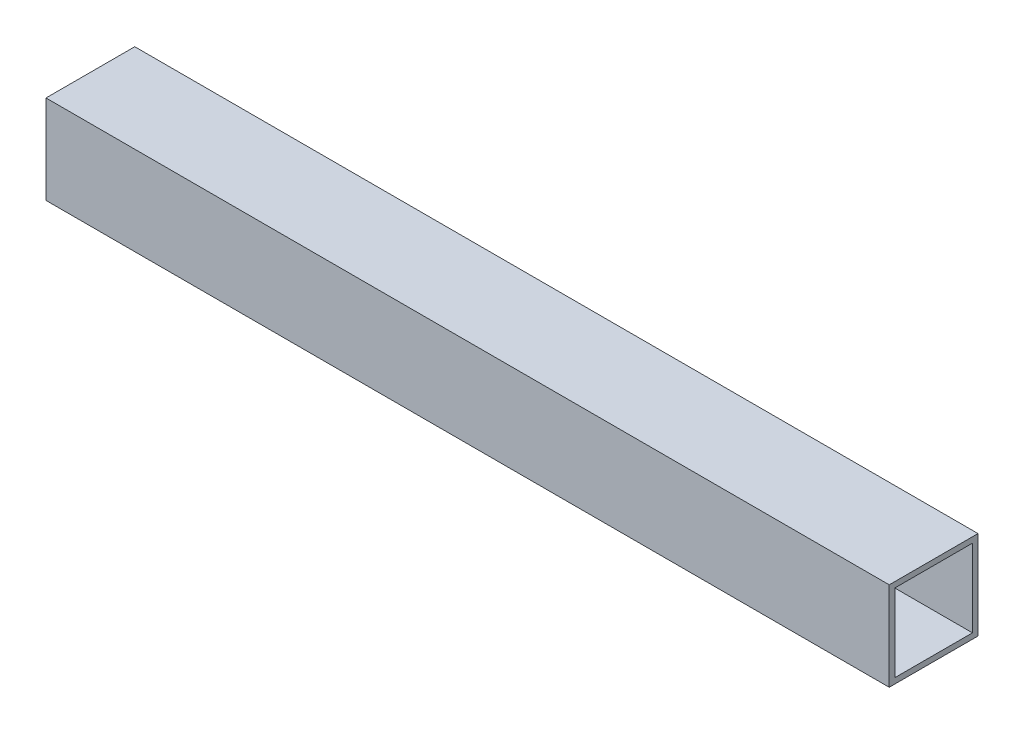
SolidWorks part; units mm, degrees
material "6061-T6 (SS)"
ref_plane "Front" through (0, 0, 0) normal (0, 0, 1) x (1, 0, 0)
ref_plane "Top" through (0, 0, 0) normal (0, 1, 0) x (1, 0, 0)
ref_plane "Right" through (0, 0, 0) normal (1, 0, 0) x (0, 0, -1)
sketch "Sketch1" plane through (0, 0, 0) normal (1, 0, 0) x (0, 0, -1)
  line L1 (12.7, -12.7) -> (-12.7, -12.7)
  line L2 (12.7, -12.7) -> (12.7, 12.7)
  line L3 (12.7, 12.7) -> (-12.7, 12.7)
  line L4 (-12.7, -12.7) -> (-12.7, 12.7)
  line L5 (12.7, -12.7) -> (-12.7, 12.7) construction
  line L6 (12.7, 12.7) -> (-12.7, -12.7) construction
  point P0 (0, 0)
  dimension "D1" = 25.4
extrude "Extrude-Thin1" add sketch "Sketch1" along normal up to surface (241.3 mm away) thin thin type one direction reverse wall 1.5875
